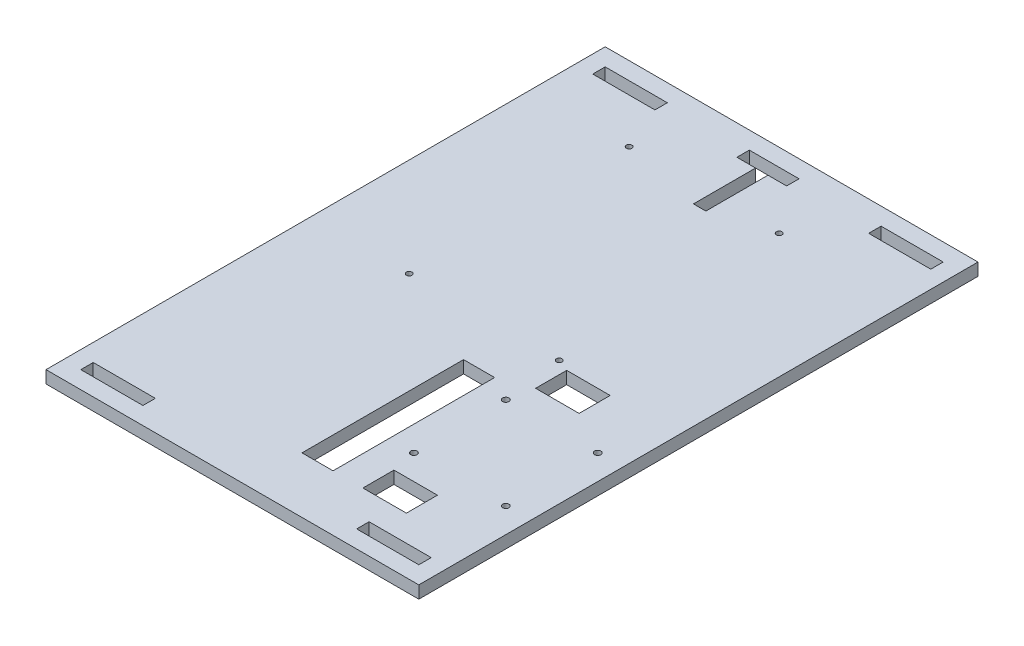
SolidWorks part; units mm, degrees
ref_plane "Front Plane" through (0, 0, 0) normal (0, 0, 1) x (1, 0, 0)
ref_plane "Top Plane" through (0, 0, 0) normal (0, 1, 0) x (1, 0, 0)
ref_plane "Right Plane" through (0, 0, 0) normal (1, 0, 0) x (0, 0, -1)
sketch "Sketch1" plane through (0, 0, 0) normal (0, 1, 0) x (1, 0, 0)
  line L1 (-75, 112.5) -> (75, 112.5)
  line L2 (-75, 112.5) -> (-75, -112.5)
  line L3 (-75, -112.5) -> (75, -112.5)
  line L4 (75, 112.5) -> (75, -112.5)
  point P4 (0, 112.5)
  point P6 (-75, 0)
  dimension "D1" = 150
  dimension "D2" = 225
extrude "Boss-Extrude1" add sketch "Sketch1" along normal blind 5
sketch "Sketch2" plane through (0, 5, 0) normal (0, 1, 0) x (1, 0, 0)
  line L0 (-35.35, 82.5) -> (25, 82.5) construction
  line L1 (-35.35, 82.5) -> (-35.35, -6) construction
  circle A0 centre (-35.35, 82.5) radius 1.125
  circle A1 centre (25, 82.5) radius 1.125
  circle A2 centre (25, -6) radius 1.125
  circle A3 centre (-35.35, -6) radius 1.125
  dimension "D3" = 2.25
  dimension "D1" = 60.35
  dimension "D2" = 88.5
  dimension "D4" = 30
  dimension "D5" = 50
sketch "Sketch3" plane through (0, 5, 0) normal (0, 1, 0) x (1, 0, 0)
  line L0 (28, -30.5) -> (28, -67.5) construction
  line L1 (28, -30.5) -> (65, -30.5) construction
  circle A0 centre (28, -30.5) radius 1.275
  circle A1 centre (65, -30.5) radius 1.275
  circle A2 centre (65, -67.5) radius 1.275
  circle A3 centre (28, -67.5) radius 1.275
  dimension "D1" = 2.55
  dimension "D2" = 37
  dimension "D3" = 45
  dimension "D4" = 10
sketch "Sketch6" plane through (0, 5, 0) normal (0, 1, 0) x (1, 0, 0)
  line L10 (-10, 105.5) -> (10, 105.5)
  line L11 (-10, 105.5) -> (-10, 100.5)
  line L12 (-10, 100.5) -> (10, 100.5)
  line L13 (10, 105.5) -> (10, 100.5)
  point P4 (0, 105.5)
  dimension "D1" = 20
  dimension "D2" = 7
  dimension "D3" = 5
extrude "Cut-Extrude1" cut sketch "Sketch2" against normal through all
extrude "Cut-Extrude2" cut sketch "Sketch3" against normal through all
extrude "Cut-Extrude3" cut sketch "Sketch6" against normal through all
sketch "Sketch9" plane through (0, 5, 0) normal (0, 1, 0) x (1, 0, 0)
  line L1 (5.5, -90) -> (18, -90)
  line L2 (5.5, -90) -> (5.5, -25)
  line L3 (5.5, -25) -> (18, -25)
  line L4 (18, -90) -> (18, -25)
  line L5 (30, -8) -> (47.5, -8)
  line L6 (30, -8) -> (30, -20.5)
  line L7 (30, -20.5) -> (47.5, -20.5)
  line L8 (47.5, -8) -> (47.5, -20.5)
  line L9 (30, -77.5) -> (47.5, -77.5)
  line L10 (30, -77.5) -> (30, -90)
  line L11 (30, -90) -> (47.5, -90)
  line L12 (47.5, -77.5) -> (47.5, -90)
  circle A0 centre (28, -30.5) radius 1.275 construction
  circle A1 centre (28, -67.5) radius 1.275 construction
  dimension "D1" = 2
  dimension "D5" = 10
  dimension "D2" = 12.5
  dimension "D3" = 17.5
  dimension "D4" = 10
  dimension "D6" = 10
  dimension "D7" = 12.5
  dimension "D8" = 65
extrude "Cut-Extrude4" cut sketch "Sketch9" against normal up to surface (5 mm away) up to face at (0, 0, -103)
sketch "Sketch10" plane through (0, 5, 0) normal (0, 1, 0) x (1, 0, 0)
  line L0 (0, 0) -> (-75, 0) construction
  line L1 (-68, -105.5) -> (-43, -105.5)
  line L2 (-68, -105.5) -> (-68, -100.5)
  line L3 (-68, -100.5) -> (-43, -100.5)
  line L4 (-43, -105.5) -> (-43, -100.5)
  line L9 (-75, 112.5) -> (-75, -112.5) construction
  line L10 (0, 0) -> (0, -112.5) construction
  line L11 (-75, -112.5) -> (75, -112.5) construction
  line L12 (-68, 100.5) -> (-43, 100.5)
  line L13 (-43, 105.5) -> (-43, 100.5)
  line L14 (-68, 105.5) -> (-43, 105.5)
  line L15 (-68, 105.5) -> (-68, 100.5)
  line L16 (68, -100.5) -> (43, -100.5)
  line L17 (43, -105.5) -> (43, -100.5)
  line L18 (68, -105.5) -> (43, -105.5)
  line L19 (68, -105.5) -> (68, -100.5)
  line L20 (68, 105.5) -> (68, 100.5)
  line L21 (68, 105.5) -> (43, 105.5)
  line L22 (43, 105.5) -> (43, 100.5)
  line L23 (68, 100.5) -> (43, 100.5)
  dimension "D1" = 7
  dimension "D2" = 7
  dimension "D3" = 5
  dimension "D4" = 25
extrude "Cut-Extrude5" cut sketch "Sketch10" against normal up to surface (5 mm away) up to face at (11.75, 0, 57.5)
sketch "Sketch11" plane through (0, 5, 0) normal (0, 1, 0) x (1, 0, 0)
  line L0 (-10, 100.5) -> (10, 100.5) construction
  line L1 (-2.5, 100.5) -> (2.5, 100.5)
  line L2 (2.5, 100.5) -> (2.5, 75.5)
  line L3 (2.5, 75.5) -> (-2.5, 75.5)
  line L4 (-2.5, 75.5) -> (-2.5, 100.5)
  point P6 (0, 100.5)
  point P9 (0, 100.5)
  dimension "D1" = 5
  dimension "D2" = 25
extrude "Cut-Extrude6" cut sketch "Sketch11" against normal up to surface (5 mm away) up to face at (-55.5, 0, -103)
